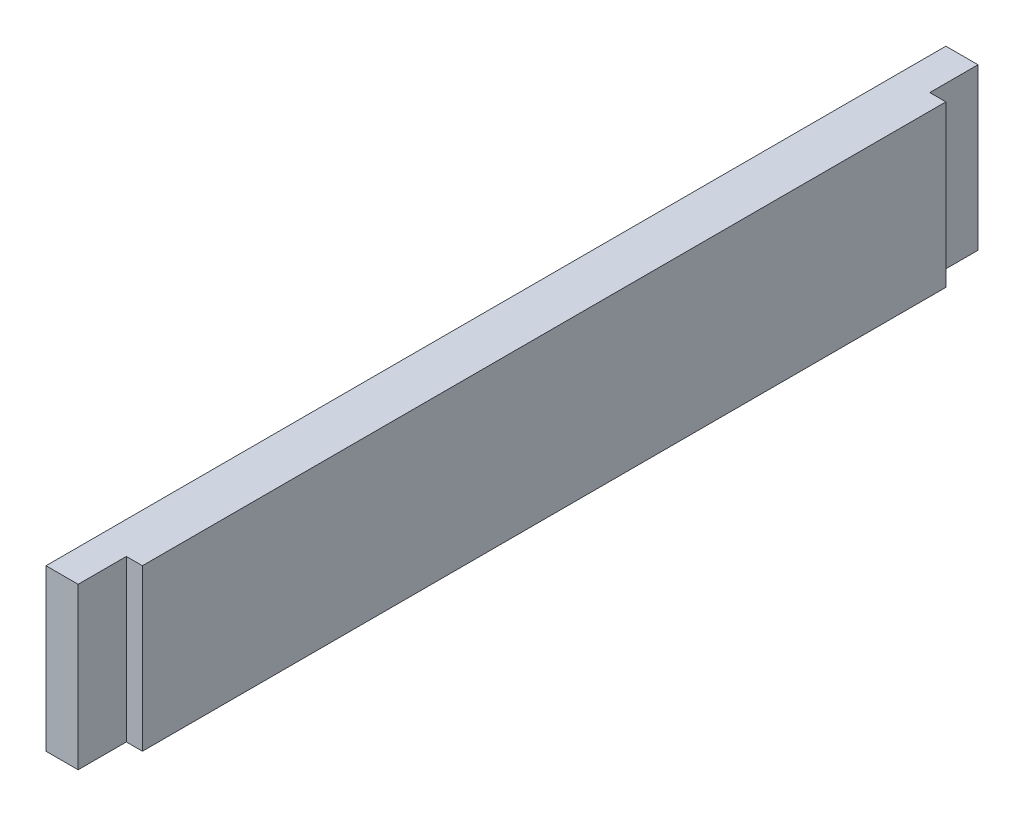
SolidWorks part; units mm, degrees
note: '?' marks a value the reader was unsure of.
material "Mahogany"
ref_plane "Front Plane" through (0, 0, 0) normal (0, 0, 1) x (1, 0, 0)
ref_plane "Top Plane" through (0, 0, 0) normal (0, 1, 0) x (1, 0, 0)
ref_plane "Right Plane" through (0, 0, 0) normal (1, 0, 0) x (0, 0, -1)
ref_axis "X-Axis" through (-88.99, 0, 0) along (1, 0, 0)?
ref_axis "Y-Axis" through (0, 55, 0) along (0, -1, 0)?
ref_axis "Z-Axis" through (0, 0, -88.99) along (0, 0, 1)?
sketch "Sketch2" plane through (0, 0, 0) normal (0, 1, 0) x (1, 0, 0)
  line L0 (-171.45, 88.9) -> (-171.45, -88.9) construction
  line L1 (-171.45, 88.9) -> (-171.45, -88.9)
  line L2 (-171.45, 88.9) -> (-165.1, 88.9)
  line L3 (-165.1, 88.9) -> (-165.1, 79.375)
  line L4 (-165.1, 79.375) -> (-161.925, 79.375)
  line L5 (-161.925, 79.375) -> (-161.925, 34.925)
  line L9 (-161.925, 25.4) -> (-161.925, -79.375)
  line L10 (-161.925, -79.375) -> (-165.1, -79.375)
  line L11 (-165.1, -79.375) -> (-165.1, -88.9)
  line L12 (171.45, -88.9) -> (-171.45, -88.9) construction
  line L13 (-165.1, -88.9) -> (-165.1, -79.375) construction
  line L14 (-165.1, -88.9) -> (-171.45, -88.9)
  line L15 (-161.925, 25.4) -> (-161.925, 34.925)
extrude "Boss-Extrude1" add sketch "Sketch2" along normal up to vertex (15.875 mm away) and the other way up to vertex (15.875 mm away)
